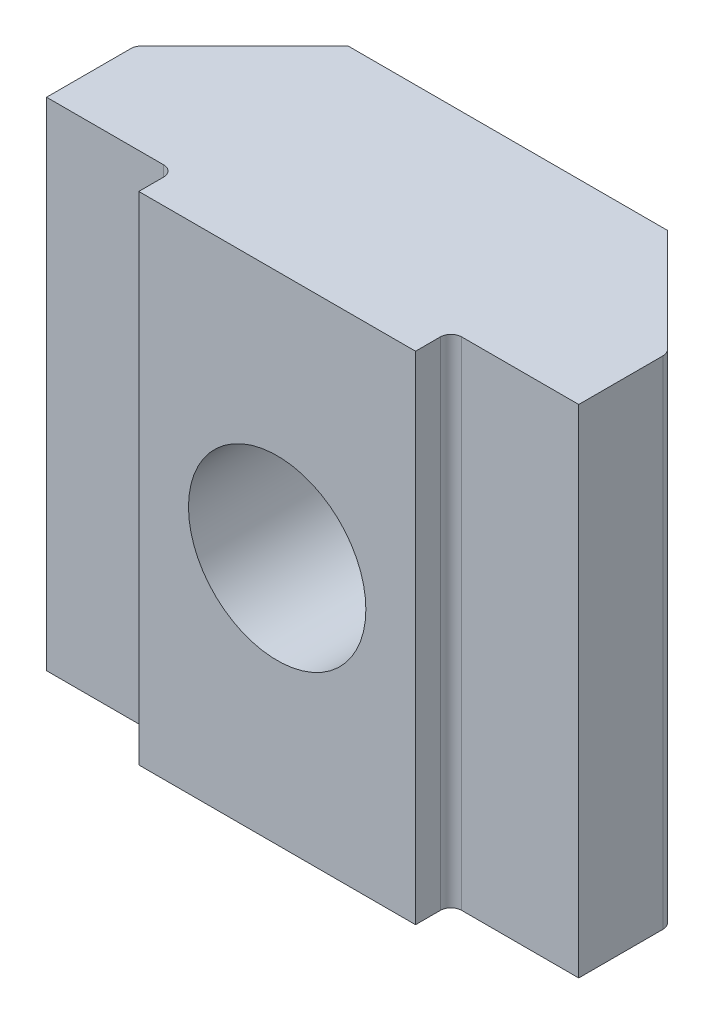
SolidWorks part; units mm, degrees
material "Acciaio inossidabile al cromo"
ref_plane "Front Plane" through (0, 0, 0) normal (0, 0, 1) x (1, 0, 0)
ref_plane "Top Plane" through (0, 0, 0) normal (0, 1, 0) x (1, 0, 0)
ref_plane "Right Plane" through (0, 0, 0) normal (1, 0, 0) x (0, 0, -1)
sketch "Sketch1" plane through (0, 0, 0) normal (0, 0, 1) x (1, 0, 0)
  line L1 (7.5, -7) -> (-7.5, -7)
  line L2 (7.5, -7) -> (7.5, 7)
  line L3 (7.5, 7) -> (-7.5, 7)
  line L4 (-7.5, -7) -> (-7.5, 7)
  line L5 (7.5, -7) -> (-7.5, 7) construction
  line L6 (7.5, 7) -> (-7.5, -7) construction
  point P0 (0, 0)
  dimension "D1" = 15
  dimension "D2" = 14
extrude "Extrude1" add sketch "Sketch1" against normal blind 5.5
sketch "Sketch2" plane through (0, 0, 0) normal (0, 0, 1) x (1, 0, 0)
  line L0 (7.5, 7) -> (-7.5, 7) construction
  line L1 (3.9, -7) -> (-3.9, -7)
  line L2 (3.9, -7) -> (3.9, 7)
  line L3 (3.9, 7) -> (-3.9, 7)
  line L4 (-3.9, -7) -> (-3.9, 7)
  line L5 (3.9, -7) -> (-3.9, 7) construction
  line L6 (3.9, 7) -> (-3.9, -7) construction
  point P0 (0, 0)
  dimension "D1" = 7.8
extrude "Extrude2" add sketch "Sketch2" along normal blind 1
sketch "Sketch6" plane through (0, 0, -5.5) normal (0, 0, -1) x (-1, 0, 0)
  point P0 (0, 0)
hole_wizard "M6x1.0 Tapped Hole1" positions "3DSketch3" profile "Sketch7" tap size "M6x1.0" standard "Ansi Metric" end condition through all
sketch3d "3DSketch3"
  point P0 (0, 0, 0)
  point P3 (0, 0, -5.5)
sketch "Sketch7" plane through (0, 0, -5.5) normal (1, 0, 0) x (0, 1, 0)
  line L0 (0, 0) -> (0, 6.5)
  line L1 (0, 6.5) -> (2.5, 6.5)
  line L2 (2.5, 6.5) -> (2.5, 0)
  line L5 (2.5, 0) -> (0, 0)
  line L11 (0, -6.35) -> (0, 107.95) construction
  dimension "Thru Tap Drill Dia." = 5
  dimension "Thru Tap Drill Depth" = 6.5
cosmetic thread "Cosmetic Thread1" parameters "D2"=6
cosmetic thread "Cosmetic Thread2" parameters "D2"=6
chamfer "Chamfer1" distance 3 angle 45 2 edges at (7.5, 0, -5.5) (-7.5, 0, -5.5)
fillet "Fillet1" radius 0.3 4 edges at (7.5, 0, -2.5) (-7.5, 0, -2.5)
